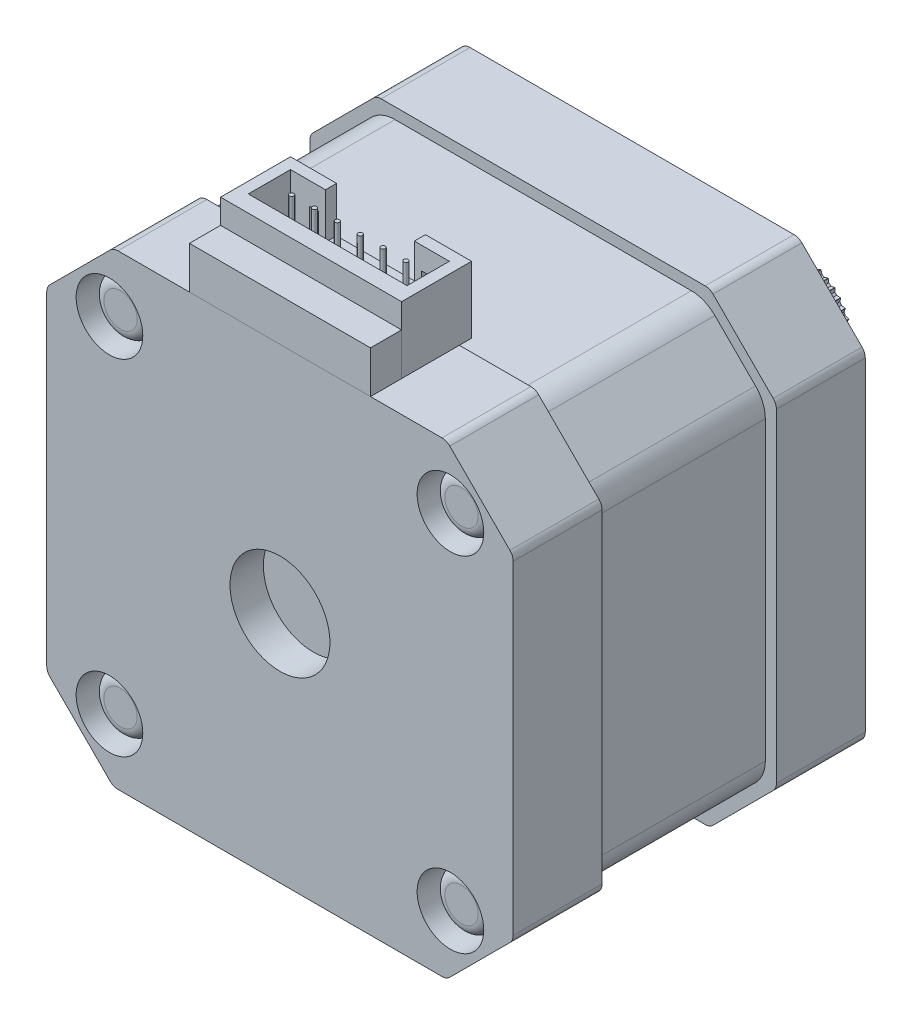
SolidWorks part; units mm, degrees
ref_plane "Front Plane" through (0, 0, 0) normal (0, 0, 1) x (1, 0, 0)
ref_plane "Top Plane" through (0, 0, 0) normal (0, 1, 0) x (1, 0, 0)
ref_plane "Right Plane" through (0, 0, 0) normal (1, 0, 0) x (0, 0, -1)
sketch "Sketch1" plane through (0, 0, 0) normal (0, 0, 1) x (1, 0, 0)
  line L1 (-21, 21) -> (21, 21)
  line L2 (-21, 21) -> (-21, -21)
  line L3 (-21, -21) -> (21, -21)
  line L4 (21, 21) -> (21, -21)
  line L5 (-21, 21) -> (21, -21) construction
  line L6 (-21, -21) -> (21, 21) construction
  point P0 (0, 0)
  dimension "D1" = 42
  dimension "D2" = 42
extrude "Boss-Extrude1" add sketch "Sketch1" along normal blind 8
chamfer "Chamfer1" distance 6 angle 45 4 edges at (-21, -21, 4) (21, -21, 4) (21, 21, 4) (-21, 21, 4)
fillet "Fillet1" radius 1 8 edges at (-15, 21, 4) (-21, 15, 4) (-21, -15, 4) (-15, -21, 4) (15, -21, 4) (21, -15, 4) (21, 15, 4) (15, 21, 4)
sketch "Sketch3" plane through (0, 0, 0) normal (0, 0, -1) x (-1, 0, 0)
  line L0 (-14.5858, 21) -> (14.5858, 21) construction
  line L1 (-15.2929, 20.7071) -> (-20.7071, 15.2929) construction
  line L2 (-21, -14.5858) -> (-21, 14.5858) construction
  line L3 (20.7071, 15.2929) -> (15.2929, 20.7071) construction
  line L4 (21, 14.5858) -> (21, -14.5858) construction
  line L5 (15.2929, -20.7071) -> (20.7071, -15.2929) construction
  line L6 (14.5858, -21) -> (-14.5858, -21) construction
  line L7 (-20.7071, -15.2929) -> (-15.2929, -20.7071) construction
  line L8 (-14.5858, 21) -> (14.5858, 21)
  line L9 (-15.2929, 20.7071) -> (-20.7071, 15.2929)
  line L10 (-21, -14.5858) -> (-21, 14.5858)
  line L11 (20.7071, 15.2929) -> (15.2929, 20.7071)
  line L12 (21, 14.5858) -> (21, -14.5858)
  line L13 (15.2929, -20.7071) -> (20.7071, -15.2929)
  line L14 (14.5858, -21) -> (-14.5858, -21)
  line L15 (-20.7071, -15.2929) -> (-15.2929, -20.7071)
  line L16 (-14.5858, 20) -> (14.5858, 20)
  line L17 (20, 14.5858) -> (14.5858, 20)
  line L18 (20, 14.5858) -> (20, -14.5858)
  line L19 (14.5858, -20) -> (20, -14.5858)
  line L20 (14.5858, -20) -> (-14.5858, -20)
  line L21 (-20, -14.5858) -> (-14.5858, -20)
  line L22 (-20, -14.5858) -> (-20, 14.5858)
  line L23 (-14.5858, 20) -> (-20, 14.5858)
  arc A0 (20.7071, -15.2929) -> (21, -14.5858) centre (20, -14.5858) ccw construction
  arc A1 (14.5858, -21) -> (15.2929, -20.7071) centre (14.5858, -20) ccw construction
  arc A2 (-15.2929, -20.7071) -> (-14.5858, -21) centre (-14.5858, -20) ccw construction
  arc A3 (-21, -14.5858) -> (-20.7071, -15.2929) centre (-20, -14.5858) ccw construction
  arc A4 (15.2929, 20.7071) -> (14.5858, 21) centre (14.5858, 20) ccw construction
  arc A5 (21, 14.5858) -> (20.7071, 15.2929) centre (20, 14.5858) ccw construction
  arc A6 (-14.5858, 21) -> (-15.2929, 20.7071) centre (-14.5858, 20) ccw construction
  arc A7 (-20.7071, 15.2929) -> (-21, 14.5858) centre (-20, 14.5858) ccw construction
  arc A8 (20.7071, -15.2929) -> (21, -14.5858) centre (20, -14.5858) ccw
  arc A9 (14.5858, -21) -> (15.2929, -20.7071) centre (14.5858, -20) ccw
  arc A10 (-15.2929, -20.7071) -> (-14.5858, -21) centre (-14.5858, -20) ccw
  arc A11 (-21, -14.5858) -> (-20.7071, -15.2929) centre (-20, -14.5858) ccw
  arc A12 (15.2929, 20.7071) -> (14.5858, 21) centre (14.5858, 20) ccw
  arc A13 (21, 14.5858) -> (20.7071, 15.2929) centre (20, 14.5858) ccw
  arc A14 (-14.5858, 21) -> (-15.2929, 20.7071) centre (-14.5858, 20) ccw
  arc A15 (-20.7071, 15.2929) -> (-21, 14.5858) centre (-20, 14.5858) ccw
  arc A16 (14.5858, 20) -> (14.5858, 20) centre (14.5858, 20) ccw
  arc A17 (20, 14.5858) -> (20, 14.5858) centre (20, 14.5858) ccw
  arc A18 (20, -14.5858) -> (20, -14.5858) centre (20, -14.5858) ccw
  arc A19 (14.5858, -20) -> (14.5858, -20) centre (14.5858, -20) ccw
  arc A20 (-14.5858, -20) -> (-14.5858, -20) centre (-14.5858, -20) ccw
  arc A21 (-20, -14.5858) -> (-20, -14.5858) centre (-20, -14.5858) ccw
  arc A22 (-20, 14.5858) -> (-20, 14.5858) centre (-20, 14.5858) ccw
  arc A23 (-14.5858, 20) -> (-14.5858, 20) centre (-14.5858, 20) ccw
  dimension "D1" = 1
extrude "Boss-Extrude4" add sketch "Sketch3" along normal blind 15.7 separate body contours L16 A16 L17 A17 L18 A18 L19 A19 L20 A20 L21 A21 L22 A22 L23 A23
fillet "Fillet2" radius 3 8 edges at (20, -14.5858, -7.85) (14.5858, -20, -7.85) (-14.5858, -20, -7.85) (-20, -14.5858, -7.85) (-20, 14.5858, -7.85) (-14.5858, 20, -7.85) (20, 14.5858, -7.85) (14.5858, 20, -7.85)
sketch "Sketch6" plane through (0, 0, -15.7) normal (0, 0, -1) x (-1, 0, 0)
  line L0 (15.2929, -20.7071) -> (20.7071, -15.2929) construction
  line L1 (14.5858, -21) -> (-14.5858, -21) construction
  line L2 (-20.7071, -15.2929) -> (-15.2929, -20.7071) construction
  line L3 (-21, -14.5858) -> (-21, 14.5858) construction
  line L4 (-15.2929, 20.7071) -> (-20.7071, 15.2929) construction
  line L5 (-14.5858, 21) -> (14.5858, 21) construction
  line L6 (20.7071, 15.2929) -> (15.2929, 20.7071) construction
  line L7 (21, 14.5858) -> (21, -14.5858) construction
  line L8 (15.2929, -20.7071) -> (20.7071, -15.2929)
  line L9 (14.5858, -21) -> (-14.5858, -21)
  line L10 (-20.7071, -15.2929) -> (-15.2929, -20.7071)
  line L11 (-21, -14.5858) -> (-21, 14.5858)
  line L12 (-15.2929, 20.7071) -> (-20.7071, 15.2929)
  line L13 (-14.5858, 21) -> (14.5858, 21)
  line L14 (20.7071, 15.2929) -> (15.2929, 20.7071)
  line L15 (21, 14.5858) -> (21, -14.5858)
  arc A0 (20.7071, -15.2929) -> (21, -14.5858) centre (20, -14.5858) ccw construction
  arc A1 (14.5858, -21) -> (15.2929, -20.7071) centre (14.5858, -20) ccw construction
  arc A2 (-15.2929, -20.7071) -> (-14.5858, -21) centre (-14.5858, -20) ccw construction
  arc A3 (-21, -14.5858) -> (-20.7071, -15.2929) centre (-20, -14.5858) ccw construction
  arc A4 (-20.7071, 15.2929) -> (-21, 14.5858) centre (-20, 14.5858) ccw construction
  arc A5 (-14.5858, 21) -> (-15.2929, 20.7071) centre (-14.5858, 20) ccw construction
  arc A6 (15.2929, 20.7071) -> (14.5858, 21) centre (14.5858, 20) ccw construction
  arc A7 (21, 14.5858) -> (20.7071, 15.2929) centre (20, 14.5858) ccw construction
  arc A8 (20.7071, -15.2929) -> (21, -14.5858) centre (20, -14.5858) ccw
  arc A9 (14.5858, -21) -> (15.2929, -20.7071) centre (14.5858, -20) ccw
  arc A10 (-15.2929, -20.7071) -> (-14.5858, -21) centre (-14.5858, -20) ccw
  arc A11 (-21, -14.5858) -> (-20.7071, -15.2929) centre (-20, -14.5858) ccw
  arc A12 (-20.7071, 15.2929) -> (-21, 14.5858) centre (-20, 14.5858) ccw
  arc A13 (-14.5858, 21) -> (-15.2929, 20.7071) centre (-14.5858, 20) ccw
  arc A14 (15.2929, 20.7071) -> (14.5858, 21) centre (14.5858, 20) ccw
  arc A15 (21, 14.5858) -> (20.7071, 15.2929) centre (20, 14.5858) ccw
extrude "Boss-Extrude5" add sketch "Sketch6" along normal blind 8 separate body
sketch "Sketch7" plane through (0, 0, 8) normal (0, 0, 1) x (1, 0, 0)
  line L0 (-15.35, 15.5) -> (15.35, 15.5) construction
  line L1 (-15.35, -15.5) -> (15.35, -15.5) construction
  line L2 (14.5858, 21) -> (-14.5858, 21) construction
  line L3 (15.35, 15.5) -> (20.5, 15.5) construction
  line L4 (20.7071, 15.2929) -> (15.2929, 20.7071) construction
  line L5 (-15.35, 15.5) -> (-20.5, 15.5) construction
  line L6 (-15.2929, 20.7071) -> (-20.7071, 15.2929) construction
  line L7 (-14.5858, -21) -> (14.5858, -21) construction
  circle A0 centre (-15.35, 15.5) radius 1.5
  circle A1 centre (15.35, 15.5) radius 1.5
  circle A2 centre (15.35, -15.5) radius 1.5
  circle A3 centre (-15.35, -15.5) radius 1.5
  dimension "D1" = 30.7
  dimension "D2" = 3
  dimension "D3" = 5.5
  dimension "D4" = 5.5
extrude "Cut-Extrude1" cut sketch "Sketch7" against normal through all
sketch "Sketch8" plane through (0, 0, -23.7) normal (0, 0, -1) x (-1, 0, 0)
  circle A0 centre (0, 0) radius 4.5
  dimension "D1" = 9
extrude "Cut-Extrude2" cut sketch "Sketch8" against normal through all
sketch "Sketch9" plane through (0, 0, -23.7) normal (0, 0, -1) x (-1, 0, 0)
  circle A0 centre (0, 0) radius 11
  circle A1 centre (0, 0) radius 4.5 construction
  circle A2 centre (0, 0) radius 4.5
  dimension "D1" = 22
extrude "Boss-Extrude7" add sketch "Sketch9" along normal blind 1.8
fillet "Fillet4" radius 0.5 1 edges at (-11, 0, -23.7)
fillet "Fillet5" radius 0.2 1 edges at (-11, 0, -25.5)
ref_plane "Plane2" through (0, 0, 5) normal (0, 0, 1) x (1, 0, 0)
sketch "Sketch12" plane through (0, 0, 5) normal (0, 0, 1) x (1, 0, 0)
  circle A0 centre (0, 0) radius 4.5 construction
  circle A1 centre (0, 0) radius 4.5
extrude "Boss-Extrude8" add sketch "Sketch12" against normal blind 10 separate body
sketch "Sketch16" plane through (0, 0, -5) normal (0, 0, -1) x (-1, 0, 0)
  line L0 (0, 2.25) -> (2.25, 0)
  arc A0 (0, 2.25) -> (2.25, 0) centre (0, 0) ccw
  dimension "D1" = 4.5
extrude "Boss-Extrude9" add sketch "Sketch16" along normal blind 34
sketch "Sketch17" plane through (0, 0, -39) normal (0, 0, -1) x (-1, 0, 0)
  line L0 (2.25, 0) -> (0, 2.25) construction
  line L1 (2.25, 0) -> (0, 2.25)
  arc A0 (0, 2.25) -> (2.25, 0) centre (0, 0) ccw construction
  arc A1 (0, 2.25) -> (2.25, 0) centre (0, 0) ccw
  circle A2 centre (0, 0) radius 4.5
  circle A3 centre (0, 0) radius 4.25
  arc M1 (0, 2.25) -> (2.25, 0) centre (0, 0) ccw
  line M2 (2.25, 0) -> (0, 2.25)
  dimension "D1" = 9
  dimension "4" = 8.5
extrude "Boss-Extrude10" add sketch "Sketch17" against normal blind 9 separate body contours A3 M1 M2 | A2 A3 region at (4.3727, 0, -39) region at (4.1298, 0, -39)
sketch "Sketch18" plane through (0, 0, -39) normal (0, 0, -1) x (-1, 0, 0)
  line L0 (0, 4.25) -> (-0.2434, 4.4934)
  line L1 (0.4765, 4.4747) -> (0.2447, 4.2429)
  circle A0 centre (0, 0) radius 4.25 construction
  circle A1 centre (0, 0) radius 4.5 construction
  circle A2 centre (0, 0) radius 4.25
  circle A3 centre (0, 0) radius 4.5
  circle M3 centre (0, 0) radius 4.5
  dimension "D1" = 270
extrude "Cut-Extrude3" cut sketch "Sketch18" against normal up to next (9 mm away) contours A2 L1 L0 M3 region at (-0.119, 4.3911, -39)
pattern_circular "CirPattern1" count 38 over 360 about axis through (0, 0, -39) along (0, 0, -1) of "Cut-Extrude3"
sketch "Sketch24" plane through (0, 0, 8) normal (0, 0, 1) x (1, 0, 0)
  line L0 (14.5858, 21) -> (-14.5858, 21) construction
  line L1 (-8.15, 24.8) -> (8.15, 24.8)
  line L2 (-8.15, 24.8) -> (-8.15, 21)
  line L3 (-8.15, 21) -> (8.15, 21)
  line L4 (8.15, 24.8) -> (8.15, 21)
  line L5 (-8.15, 21) -> (-14.5858, 21) construction
  line L6 (8.15, 21) -> (14.5858, 21) construction
  arc A0 (-14.5858, 21) -> (-15.2929, 20.7071) centre (-14.5858, 20) ccw construction
  dimension "D1" = 16.3
  dimension "D2" = 3.8
extrude "Boss-Extrude17" add sketch "Sketch24" against normal blind 2.8 separate body
sketch "Sketch25" plane through (0, 0, 5.2) normal (0, 0, -1) x (-1, 0, 0)
  line L0 (8.15, 21) -> (-8.15, 21) construction
  line L1 (-8.15, 27) -> (8.15, 27)
  line L2 (-8.15, 27) -> (-8.15, 21)
  line L3 (-8.15, 21) -> (8.15, 21)
  line L4 (8.15, 27) -> (8.15, 21)
  dimension "D1" = 6
extrude "Boss-Extrude18" add sketch "Sketch25" along normal blind 6.3 separate body
sketch "Sketch26" plane through (0, 0, -1.1) normal (0, 0, -1) x (-1, 0, 0)
  line L0 (-8.15, 21) -> (-8.15, 27)
  line L1 (-8.15, 27) -> (-4, 27)
  line L2 (8.15, 27) -> (-8.15, 27) construction
  line L3 (-4, 27) -> (-4, 22.9)
  line L4 (-4, 22.9) -> (4, 22.9)
  line L5 (4, 22.9) -> (4, 27)
  line L6 (4, 27) -> (8.15, 27)
  line L7 (8.15, 27) -> (8.15, 21)
  line L8 (8.15, 21) -> (5.45, 21)
  line L9 (-8.15, 21) -> (8.15, 21) construction
  line L10 (5.45, 21) -> (5.45, 25)
  line L11 (5.45, 25) -> (4.65, 25)
  line L12 (4.65, 25) -> (4.65, 21.5)
  line L13 (4.65, 21.5) -> (-4.65, 21.5)
  line L14 (-4.65, 21.5) -> (-4.65, 25)
  line L15 (-4.65, 25) -> (-5.45, 25)
  line L16 (-5.45, 25) -> (-5.45, 21)
  line L17 (14.5858, 21) -> (-14.5858, 21) construction
  line L18 (-8.15, 21) -> (-5.45, 21)
  line L19 (-5.45, 21) -> (5.45, 21)
  line L20 (-4, 27) -> (4, 27)
  line M17 (-8.15, 21) -> (8.15, 21)
  line M19 (8.15, 27) -> (-8.15, 27)
  dimension "D1" = 3.5
  dimension "D2" = 3.5
  dimension "D3" = 8
  dimension "D4" = 1.4
  dimension "D5" = 0.8
  dimension "D6" = 0.5
  dimension "D7" = 2
extrude "Cut-Extrude6" cut sketch "Sketch26" against normal blind 4 contours L4 L5 L3 M19 region at (0, 24.95, -1.1)
sketch "Sketch28" plane through (0, 27, 0) normal (0, 1, 0) x (1, 0, 0)
  line L0 (-8.15, -5.2) -> (8.15, -5.2) construction
  line L1 (-7.15, 0.1) -> (7.15, 0.1)
  line L2 (-7.15, 0.1) -> (-7.15, -3.7)
  line L3 (-7.15, -3.7) -> (7.15, -3.7)
  line L4 (7.15, 0.1) -> (7.15, -3.7)
  line L5 (4, 1.1) -> (8.15, 1.1) construction
  line L6 (8.15, 1.1) -> (8.15, -5.2) construction
  line L7 (-8.15, 1.1) -> (-8.15, -5.2) construction
  dimension "D1" = 1.5
  dimension "D2" = 1
  dimension "D3" = 1
  dimension "D4" = 1
extrude "Cut-Extrude7" cut sketch "Sketch28" against normal blind 5
extrude "Cut-Extrude8" cut sketch "Sketch26<4>" against normal blind 1 contours L15 L16 L10 L11 L12 L13 L14 M17 region at (5.3339, 23, -1.1)
sketch "Sketch26<4>" plane through (0, 0, -1.1) normal (0, 0, -1) x (-1, 0, 0) same geometry as "Sketch26"
sketch "Sketch29" plane through (0, 22, 0) normal (0, 1, 0) x (1, 0, 0)
  line L0 (-5.147, -1.8) -> (-5.147, 0.1) construction
  line L1 (-4, 0.1) -> (-7.15, 0.1) construction
  line L2 (-5.147, -1.8) -> (-5.147, -3.7) construction
  line L3 (-7.15, -3.7) -> (7.15, -3.7) construction
  line L4 (5.147, -1.8) -> (7.15, -1.8) construction
  line L5 (7.15, -3.7) -> (7.15, 0.1) construction
  line L6 (-5.147, -1.8) -> (-7.15, -1.8) construction
  line L7 (-7.15, 0.1) -> (-7.15, -3.7) construction
  circle A0 centre (-5.147, -1.8) radius 0.2
  circle A1 centre (-3.0882, -1.8) radius 0.2
  circle A2 centre (-1.0294, -1.8) radius 0.2
  circle A3 centre (1.0294, -1.8) radius 0.2
  circle A4 centre (3.0882, -1.8) radius 0.2
  circle A5 centre (5.147, -1.8) radius 0.2
  dimension "D1" = 0.4
  dimension "D3" = 2.0588
  dimension "D2" = 6
extrude "Boss-Extrude19" add sketch "Sketch29" along normal blind 5
sketch "Sketch30" plane through (0, 0, 8) normal (0, 0, 1) x (1, 0, 0)
  circle A0 centre (-15.35, 15.5) radius 3
  circle A1 centre (15.35, 15.5) radius 3
  circle A2 centre (15.35, -15.5) radius 3
  circle A3 centre (-15.35, -15.5) radius 3
  circle A4 centre (-15.35, 15.5) radius 1.5 construction
  circle A5 centre (15.35, 15.5) radius 1.5 construction
  circle A6 centre (15.35, -15.5) radius 1.5 construction
  circle A7 centre (-15.35, -15.5) radius 1.5 construction
  circle A8 centre (-15.35, 15.5) radius 1.5
  circle A9 centre (15.35, 15.5) radius 1.5
  circle A10 centre (15.35, -15.5) radius 1.5
  circle A11 centre (-15.35, -15.5) radius 1.5
  dimension "D1" = 6
extrude "Cut-Extrude9" cut sketch "Sketch30" against normal blind 4
sketch "Sketch31" plane through (0, 0, 4) normal (0, 0, 1) x (1, 0, 0)
  circle A0 centre (15.35, 15.5) radius 2.5
  circle A1 centre (-15.35, 15.5) radius 2.5
  circle A2 centre (15.35, -15.5) radius 2.5
  circle A3 centre (-15.35, -15.5) radius 2.5
  dimension "D1" = 5
extrude "Boss-Extrude20" add sketch "Sketch31" along normal blind 3 separate body
fillet "Fillet6" radius 1 1 edges at (-12.85, 15.5, 7)
fillet "Fillet7" radius 1 1 edges at (17.85, 15.5, 7)
fillet "Fillet8" radius 1 1 edges at (17.85, -15.5, 7)
fillet "Fillet9" radius 1 1 edges at (-12.85, -15.5, 7)
ref_plane "Plane3" through (0, 0, 4) normal (0, 0, 1) x (1, 0, 0)
